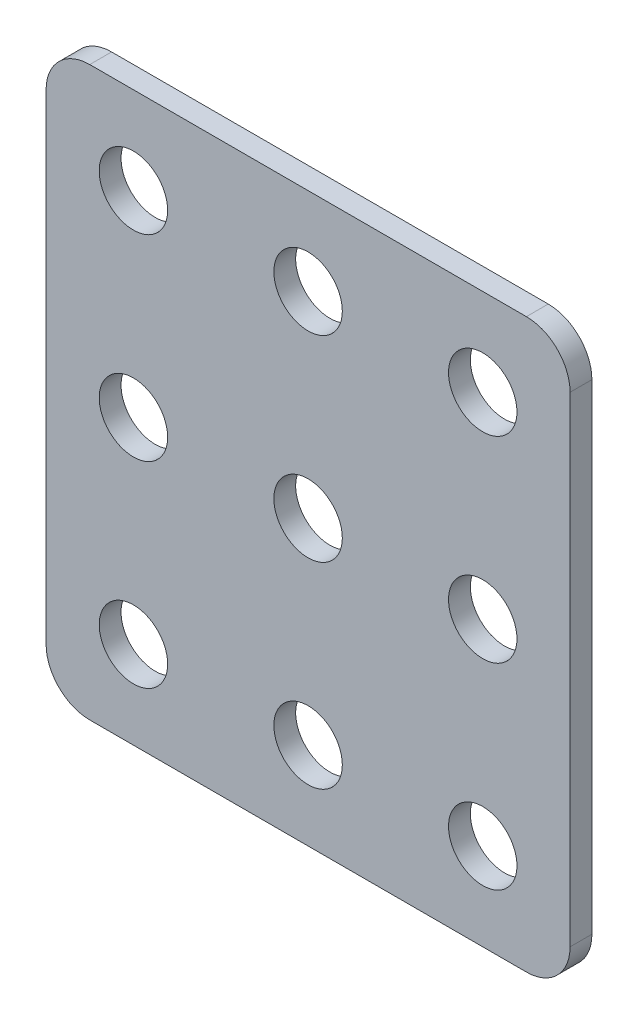
SolidWorks part; units mm, degrees
material "6061-T6 (SS)"
ref_plane "Front Plane" through (0, 0, 0) normal (0, 0, 1) x (1, 0, 0)
ref_plane "Top Plane" through (0, 0, 0) normal (0, 1, 0) x (1, 0, 0)
ref_plane "Right Plane" through (0, 0, 0) normal (1, 0, 0) x (0, 0, -1)
sketch "Sketch1" plane through (0, 0, 0) normal (0, 0, 1) x (1, 0, 0)
  line L1 (0, 0) -> (38.1, 0)
  line L2 (0, 0) -> (0, 41.275)
  line L3 (0, 41.275) -> (38.1, 41.275)
  line L4 (38.1, 0) -> (38.1, 41.275)
  circle A0 centre (6.35, 6.35) radius 2.4892
  dimension "D2" = 4.9784
  dimension "D1" = 38.1
  dimension "D3" = 6.35
  dimension "D4" = 6.35
  dimension "D5" = 41.275
extrude "Boss-Extrude1" add sketch "Sketch1" along normal mid plane 1.5875
pattern_linear "LPattern1" count 3 spacing 14.2875 along (0, 1, 0) count 3 spacing 12.7 along (1, 0, 0) of face at (8.8392, 6.35, 0.7937)
fillet "Fillet1" radius 3.175 4 edges at (0, 41.275, 0) (38.1, 0, 0) (0, 0, 0) (38.1, 41.275, 0)
